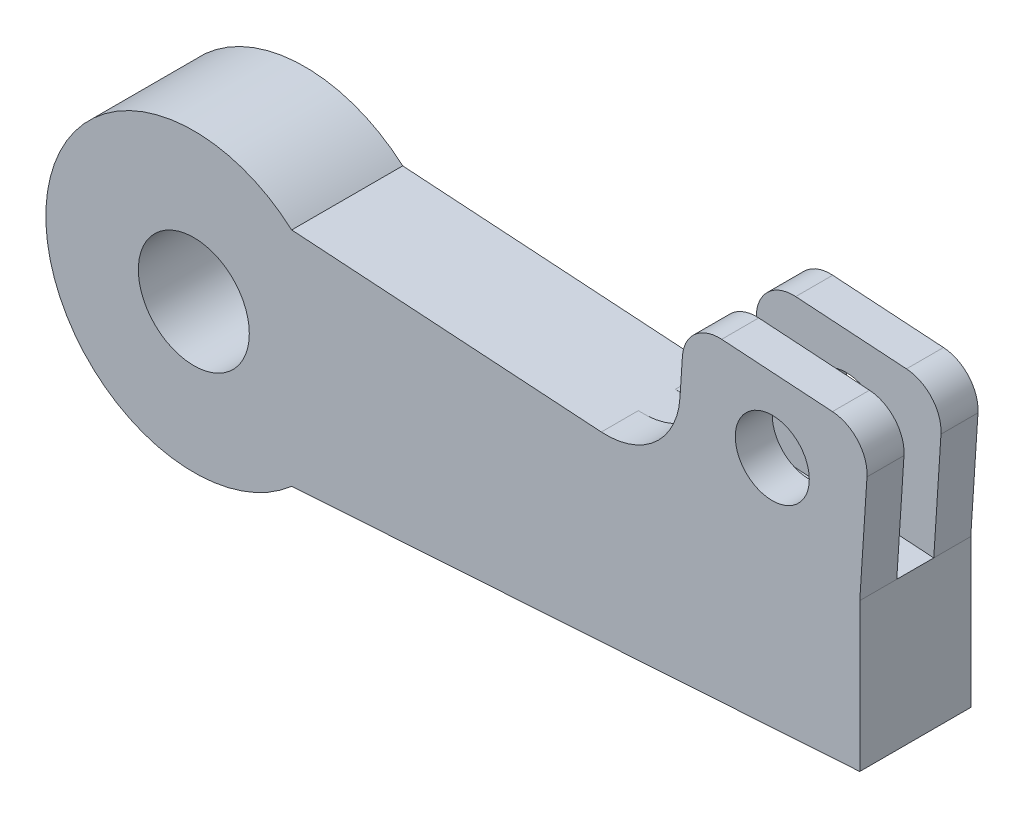
SolidWorks part; units mm, degrees
ref_plane "Front Plane" through (0, 0, 0) normal (0, 0, 1) x (1, 0, 0)
ref_plane "Top Plane" through (0, 0, 0) normal (0, 1, 0) x (1, 0, 0)
ref_plane "Right Plane" through (0, 0, 0) normal (1, 0, 0) x (0, 0, -1)
sketch "Sketch1" plane through (0, 0, 0) normal (0, 0, 1) x (1, 0, 0)
  circle A0 centre (0, 0) radius 7.5
  circle A1 centre (0, 0) radius 20
  dimension "D1" = 15
  dimension "D2" = 40
extrude "Boss-Extrude1" add sketch "Sketch1" along normal mid plane 15
sketch "Sketch2" plane through (0, 0, 0) normal (0, 0, 1) x (1, 0, 0)
  line L0 (20, 0) -> (90, 0) construction
  line L1 (13.2288, 15) -> (13.2288, -15) construction
  line L2 (13.2288, 15) -> (90, 10)
  line L3 (13.2288, -15) -> (90, -10)
  line L4 (90, -10) -> (90, 10)
  circle A0 centre (0, 0) radius 20 construction
  arc A1 (13.2288, 15) -> (13.2288, -15) centre (0, 0) cw
  point P18 (90, 0)
  dimension "D1" = 90
  dimension "D2" = 30
  dimension "D3" = 20
extrude "Boss-Extrude2" add sketch "Sketch2" along normal mid plane 15
sketch "Sketch4" plane through (1.0287, 15.7946, 0) normal (0.065, 0.9979, 0) x (0.9979, -0.065, 0)
  line L0 (0, 0) -> (89.1598, 0) construction
  line L1 (89.1598, -7.5) -> (89.1598, 7.5) construction
  line L2 (89.1598, 7.5) -> (12.2259, 7.5) construction
  line L3 (64.1598, -7.5) -> (89.1598, -7.5)
  line L4 (64.1598, -7.5) -> (64.1598, 7.5)
  line L5 (64.1598, 7.5) -> (89.1598, 7.5)
  line L6 (89.1598, -7.5) -> (89.1598, 7.5)
  line L7 (64.1598, -7.5) -> (89.1598, 7.5) construction
  line L8 (64.1598, 7.5) -> (89.1598, -7.5) construction
  line L9 (64.1598, 2.5) -> (89.1598, 2.5)
  line L10 (64.1598, -2.5) -> (89.1598, -2.5)
  line L11 (76.6598, 2.5) -> (76.6598, 0) construction
  line L12 (76.6598, 0) -> (76.6598, -2.5) construction
  point P5 (76.6598, 0)
  point P18 (64.1598, 3.7109)
  line M7 (89.1598, 7.5) -> (12.2259, 7.5)
  line M9 (12.2259, -7.5) -> (89.1598, -7.5)
  line M10 (89.1598, -7.5) -> (89.1598, 7.5)
  dimension "D1" = 25
  dimension "D2" = 5
extrude "Boss-Extrude3" add sketch "Sketch4" along normal blind 20 contours L4 L9 L6 M7 | L10 L4 M9 M10 region at (77.5264, 10.8124, 5) region at (77.5264, 10.8124, -5)
sketch "Sketch5" plane through (0, 0, 7.5) normal (0, 0, 1) x (1, 0, 0)
  line L0 (65.0529, 11.6248) -> (91.2998, 29.9577) construction
  circle A0 centre (78.1763, 20.7912) radius 5
  dimension "D1" = 10
extrude "Cut-Extrude1" cut sketch "Sketch5" against normal through all
fillet "Fillet1" radius 5 4 edges at (66.3527, 31.5825, 5) (91.2998, 29.9577, 5) (91.2998, 29.9577, -5) (66.3527, 31.5825, -5)
fillet "Fillet2" radius 10 2 edges at (65.0529, 11.6248, 5) (65.0529, 11.6248, -5)
